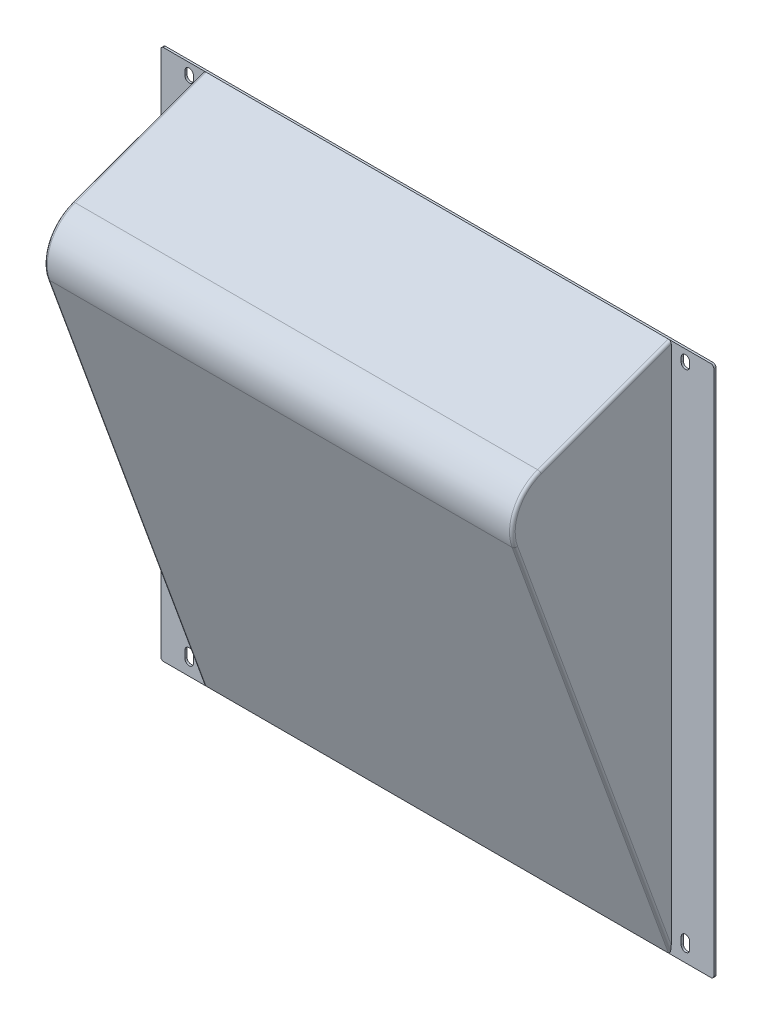
SolidWorks part; units mm, degrees
material "Q235"
ref_plane "前视基准面" through (0, 0, 0) normal (0, 0, 1) x (1, 0, 0)
ref_plane "上视基准面" through (0, 0, 0) normal (0, 1, 0) x (1, 0, 0)
ref_plane "右视基准面" through (0, 0, 0) normal (1, 0, 0) x (0, 0, -1)
sketch "草图1" plane through (0, 0, 0) normal (0, 0, 1) x (1, 0, 0)
  line L1 (-195, 187.5) -> (195, 187.5)
  line L2 (-195, 187.5) -> (-195, -187.5)
  line L3 (-195, -187.5) -> (195, -187.5)
  line L4 (195, 187.5) -> (195, -187.5)
  line L5 (-195, 187.5) -> (195, -187.5) construction
  line L6 (-195, -187.5) -> (195, 187.5) construction
  point P0 (0, 0)
  dimension "D1" = 390
  dimension "D2" = 375
extrude "凸台-拉伸1" add sketch "草图1" along normal blind 1.5
fillet "圆角1" radius 2 4 edges at (195, -187.5, 0.75) (-195, -187.5, 0.75) (-195, 187.5, 0.75) (195, 187.5, 0.75)
sketch "草图2" plane through (0, 0, 0) normal (1, 0, 0) x (0, 0, -1)
  line L0 (-1.5, 187.5) -> (-122.0227, 143.6333)
  line L1 (-1.5, -185.5) -> (-1.5, 185.5) construction
  line L3 (-1.5, -187.5) -> (-1.5, 187.5)
  line L7 (-1.5, -187.5) -> (-122.0227, 143.6333)
  dimension "D3" = 20
extrude "凸台-拉伸2" add sketch "草图2" along normal mid plane 330 contours L0 L7 L3
fillet "圆角6" radius 30 1 edges at (0, 143.6333, 122.0227)
fillet "圆角7" radius 2 6 edges at (-165, 138.3817, 110.7605) (165, 138.3817, 110.7605)
shell "抽壳1" thickness 1.5 removed face at (0, 0, 0)
sketch "草图6" plane through (0, 0, 1.5) normal (0, 0, 1) x (1, 0, 0)
  line L0 (193, 187.5) -> (163, 187.5) construction
  line L2 (0, 0) -> (0, 223.2811) construction
  line L4 (175, 178) -> (175, 181) construction
  line L5 (172, 178) -> (172, 181)
  line L6 (178, 178) -> (178, 181)
  line L7 (175, -173) -> (175, -178) construction
  line L8 (172, -173) -> (172, -178)
  line L9 (178, -173) -> (178, -178)
  line L10 (-175, 178) -> (-175, 181) construction
  line L11 (-172, 178) -> (-172, 181)
  line L12 (-178, 178) -> (-178, 181)
  line L13 (-175, -173) -> (-175, -178) construction
  line L14 (-172, -173) -> (-172, -178)
  line L15 (-178, -173) -> (-178, -178)
  arc A0 (172, 178) -> (178, 178) centre (175, 178) ccw
  arc A1 (178, 181) -> (172, 181) centre (175, 181) ccw
  arc A2 (172, -173) -> (178, -173) centre (175, -173) cw
  arc A3 (178, -178) -> (172, -178) centre (175, -178) cw
  arc A4 (-172, 178) -> (-178, 178) centre (-175, 178) cw
  arc A5 (-178, 181) -> (-172, 181) centre (-175, 181) cw
  arc A6 (-172, -173) -> (-178, -173) centre (-175, -173) ccw
  arc A7 (-178, -178) -> (-172, -178) centre (-175, -178) ccw
  point P5 (175, 179.5)
  point P13 (175, -175.5)
  point P20 (-175, 179.5)
  point P27 (-175, -175.5)
  dimension "D1" = 350
  dimension "D3" = 6
  dimension "D2" = 8
  dimension "D4" = 3
  dimension "D5" = 355
  dimension "D6" = 6
  dimension "D7" = 5
extrude "切除-拉伸3" cut sketch "草图6" against normal up to next
